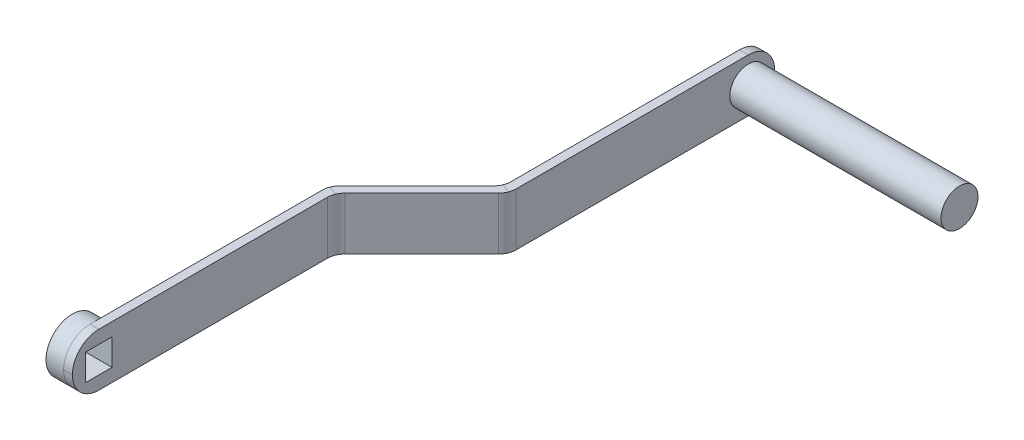
SolidWorks part; units mm, degrees
ref_plane "Front Plane" through (0, 0, 0) normal (0, 0, 1) x (1, 0, 0)
ref_plane "Top Plane" through (0, 0, 0) normal (0, 1, 0) x (1, 0, 0)
ref_plane "Right Plane" through (0, 0, 0) normal (1, 0, 0) x (0, 0, -1)
sketch "Sketch2" plane through (0, 0, 0) normal (0, 1, 0) x (1, 0, 0)
  line L0 (0, -75) -> (0, 75)
  line L1 (0, 75) -> (49.4975, 124.4975)
  line L2 (49.4975, 124.4975) -> (49.4975, 274.4975)
  point P0 (0, 0)
  point P4 (0, 0)
  dimension "D1" = 150
  dimension "D2" = 150
  dimension "D3" = 135
  dimension "D4" = 70
ref_plane "Plane1" through (0, 0, 75) normal (0, 0, 1) x (1, 0, 0)
sketch "Sketch6" plane through (0, 0, 75) normal (0, 0, 1) x (1, 0, 0)
  line L1 (-2.5, 15) -> (2.5, 15)
  line L2 (-2.5, 15) -> (-2.5, -15)
  line L3 (-2.5, -15) -> (2.5, -15)
  line L4 (2.5, 15) -> (2.5, -15)
  line L5 (-2.5, 15) -> (2.5, -15) construction
  line L6 (-2.5, -15) -> (2.5, 15) construction
  point P0 (0, 0)
  dimension "D1" = 30
  dimension "D2" = 5
sweep "Sweep1" add profiles "Sketch6" path "Sketch2"
sketch "Sketch7" plane through (-2.5, 0, 0) normal (-1, 0, 0) x (0, 0, 1)
  line L0 (75, 15) -> (-76.0355, 15) construction
  line L1 (75, 15) -> (75, -15) construction
  line L3 (52.5, 7.5) -> (67.5, 7.5)
  line L4 (52.5, 7.5) -> (52.5, -7.5)
  line L5 (52.5, -7.5) -> (67.5, -7.5)
  line L6 (67.5, 7.5) -> (67.5, -7.5)
  line L7 (52.5, 7.5) -> (67.5, -7.5) construction
  line L8 (52.5, -7.5) -> (67.5, 7.5) construction
  circle A0 centre (60, 0) radius 15
  dimension "D1" = 30
  dimension "D2" = 15
  dimension "D3" = 15
extrude "Boss-Extrude1" add sketch "Sketch7" along normal blind 10 contours A0
extrude "Cut-Extrude1" cut sketch "Sketch7<3>" against normal through all both and the other way through all contours L3 L6 L5 L4
sketch "Sketch7<3>" plane through (-2.5, 0, 0) normal (-1, 0, 0) x (0, 0, 1) same geometry as "Sketch7"
fillet "Fillet1" radius 10 4 edges at (51.9975, 0, -123.4619) (2.5, 0, -73.9645) (-2.5, 0, -76.0355) (46.9975, 0, -125.533)
fillet "Fillet2" radius 15 4 edges at (0, 15, 75) (0, -15, 75) (49.4975, -15, -274.4975) (49.4975, 15, -274.4975)
sketch "Sketch9" plane through (51.9975, 0, 0) normal (1, 0, 0) x (0, 0, -1)
  line L0 (259.4975, 15) -> (259.4975, -15) construction
  circle A0 centre (259.4975, 0) radius 10.5
  dimension "D1" = 21
extrude "Boss-Extrude2" add sketch "Sketch9" along normal blind 120
